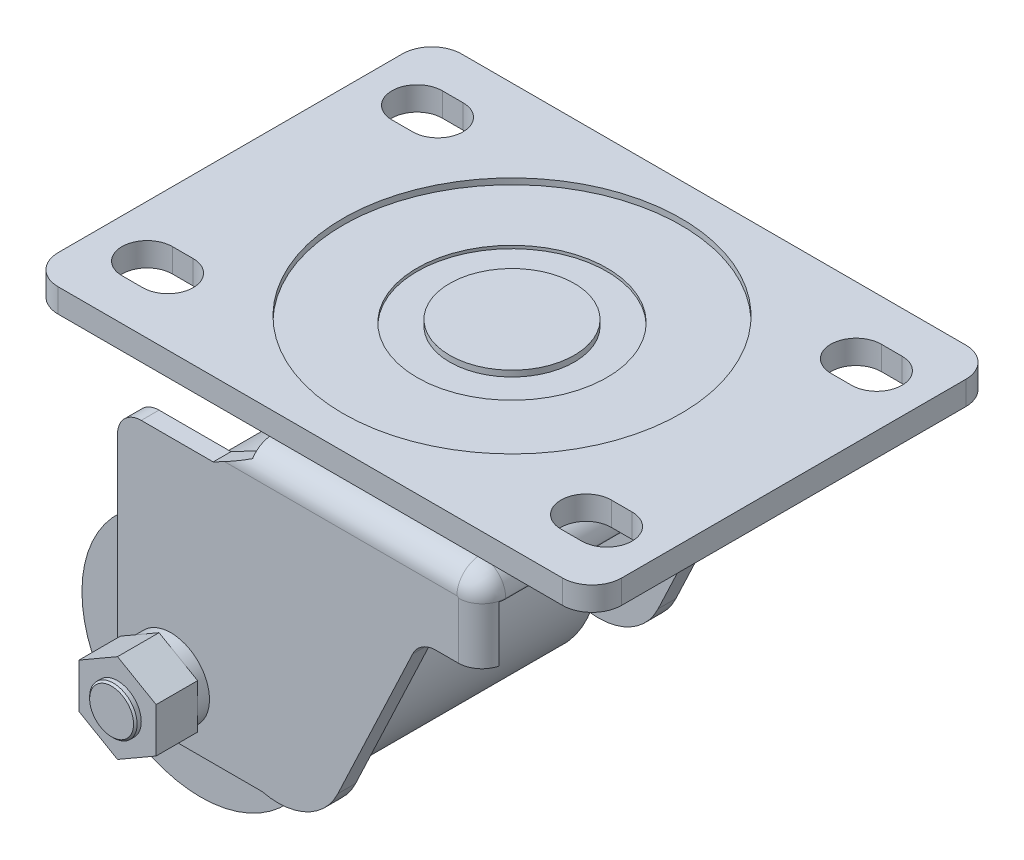
SolidWorks part; units mm, degrees
material "Plain Carbon Steel"
ref_plane "前视基准面" through (0, 0, 0) normal (0, 0, 1) x (1, 0, 0)
ref_plane "上视基准面" through (0, 0, 0) normal (0, 1, 0) x (1, 0, 0)
ref_plane "右视基准面" through (0, 0, 0) normal (1, 0, 0) x (0, 0, -1)
sketch "草图1" plane through (0, 0, 0) normal (0, 1, 0) x (1, 0, 0)
  line L1 (-47.5, -34) -> (47.5, -34)
  line L2 (-47.5, -34) -> (-47.5, 34)
  line L3 (-47.5, 34) -> (47.5, 34)
  line L4 (47.5, -34) -> (47.5, 34)
  line L5 (-47.5, -34) -> (47.5, 34) construction
  line L6 (-47.5, 34) -> (47.5, -34) construction
  point P0 (0, 0)
  dimension "D1" = 95
  dimension "D2" = 68
extrude "凸台-拉伸1" add sketch "草图1" against normal blind 4
sketch "草图2" plane through (0, 0, 0) normal (0, 1, 0) x (1, 0, 0)
  line L0 (-38.75, 22.75) -> (-35.25, 22.75) construction
  line L1 (-38.75, 27) -> (-35.25, 27)
  line L2 (-38.75, 18.5) -> (-35.25, 18.5)
  line L3 (0, 0) -> (0, 45.9781) construction
  line L4 (0, 0) -> (-36.329, 0) construction
  line L5 (38.75, 22.75) -> (35.25, 22.75) construction
  line L6 (38.75, 27) -> (35.25, 27)
  line L7 (38.75, 18.5) -> (35.25, 18.5)
  line L8 (-38.75, -22.75) -> (-35.25, -22.75) construction
  line L9 (-38.75, -27) -> (-35.25, -27)
  line L10 (-38.75, -18.5) -> (-35.25, -18.5)
  line L11 (38.75, -22.75) -> (35.25, -22.75) construction
  line L12 (38.75, -27) -> (35.25, -27)
  line L13 (38.75, -18.5) -> (35.25, -18.5)
  arc A0 (-38.75, 27) -> (-38.75, 18.5) centre (-38.75, 22.75) ccw
  arc A1 (-35.25, 18.5) -> (-35.25, 27) centre (-35.25, 22.75) ccw
  arc A2 (38.75, 27) -> (38.75, 18.5) centre (38.75, 22.75) cw
  arc A3 (35.25, 18.5) -> (35.25, 27) centre (35.25, 22.75) cw
  arc A4 (-38.75, -27) -> (-38.75, -18.5) centre (-38.75, -22.75) cw
  arc A5 (-35.25, -18.5) -> (-35.25, -27) centre (-35.25, -22.75) cw
  arc A6 (38.75, -27) -> (38.75, -18.5) centre (38.75, -22.75) ccw
  arc A7 (35.25, -18.5) -> (35.25, -27) centre (35.25, -22.75) ccw
  point P2 (-37, 22.75)
  point P13 (37, 22.75)
  point P20 (-37, -22.75)
  point P27 (37, -22.75)
  dimension "D2" = 70.5
  dimension "D4" = 45.5
  dimension "D1" = 3.5
  dimension "D3" = 8.5
extrude "切除-拉伸1" cut sketch "草图2" against normal blind 20
sketch "草图3" plane through (0, 0, 0) normal (0, 0, 1) x (1, 0, 0)
  line L0 (0, -4) -> (0, -13)
  line L1 (-47.5, -4) -> (47.5, -4) construction
  line L2 (0, -13) -> (26, -13)
  line L3 (26, -13) -> (26, -6)
  line L4 (26, -6) -> (21.6, -6)
  line L5 (21.6, -6) -> (21.6, -4)
  line L6 (21.6, -4) -> (0, -4)
  dimension "D1" = 2
  dimension "D2" = 7
  dimension "D3" = 21.6
  dimension "D4" = 26
revolve "旋转1" add sketch "草图3" angle 360 about L0
fillet "圆角3" radius 4 1 edges at (-26, -13, 0)
sketch "草图4" plane through (0, 0, 0) normal (0, 0, 1) x (1, 0, 0)
  line L0 (0, -13) -> (19.2133, -13)
  line L1 (-26, -13) -> (26, -13) construction
  line L2 (23.4482, -17.2349) -> (23.4482, -26.7145)
  line L3 (23.4482, -26.7145) -> (15.6902, -26.7145)
  line L4 (11.76, -29.205) -> (-0.8636, -55.9388)
  line L5 (-13.6125, -62) -> (-29, -62)
  line L6 (-38, -53) -> (-38, -18)
  line L7 (-38, -18) -> (-21.8692, -18)
  line L8 (-21.8692, -18) -> (-15.8691, -14.8424)
  line L9 (-15.8691, -14.8424) -> (-15.8691, -13)
  line L10 (-15.8691, -13) -> (0, -13)
  line L11 (-47.5, -4) -> (47.5, -4) construction
  line L12 (-47.5, -4) -> (-47.5, 0) construction
  arc A0 (19.2133, -13) -> (23.4482, -17.2349) centre (19.2133, -17.2349) cw
  arc A1 (15.6902, -26.7145) -> (11.76, -29.205) centre (15.6902, -31.0607) ccw
  arc A2 (-0.8636, -55.9388) -> (-13.6125, -62) centre (-10.9412, -51.1802) cw
  arc A3 (-29, -62) -> (-38, -53) centre (-29, -53) cw
  dimension "D1" = 9
  dimension "D4" = 53
  dimension "D2" = 14
  dimension "D3" = 9.5
extrude "凸台-拉伸2" add sketch "草图4" along normal mid plane 57
sketch "草图5" plane through (-38, 0, 0) normal (-1, 0, 0) x (0, 0, 1)
  line L0 (-28.5, -62.3249) -> (28.5, -62.3249) construction
  line L1 (-25.5, -62.3249) -> (25.5, -62.3249)
  line L2 (-25.5, -62.3249) -> (-25.5, -17.3249)
  line L3 (-25.5, -17.3249) -> (25.5, -17.3249)
  line L4 (25.5, -62.3249) -> (25.5, -17.3249)
  line L5 (-28.5, -18) -> (-28.5, -53) construction
  line L6 (28.5, -18) -> (28.5, -53) construction
  dimension "D1" = 45
  dimension "D2" = 3
  dimension "D3" = 3
extrude "切除-拉伸2" cut sketch "草图5" against normal through all both and the other way through all
fillet "圆角1" radius 5 4 edges at (47.5, -2, -34) (-47.5, -2, -34) (-47.5, -2, 34) (47.5, -2, 34)
sketch "草图6" plane through (0, 0, 0) normal (0, 0, 1) x (1, 0, 0)
  circle A0 centre (-29, -53) radius 20
  dimension "D1" = 40
extrude "凸台-拉伸3" add sketch "草图6" along normal mid plane 47 separate body
sketch "草图7" plane through (0, 0, 0) normal (0, 0, 1) x (1, 0, 0)
  circle A0 centre (-29, -53) radius 11.95
  dimension "D1" = 23.9
extrude "凸台-拉伸4" add sketch "草图7" along normal mid plane 50
sketch "草图8" plane through (0, 0, -28.5) normal (0, 0, -1) x (-1, 0, 0)
  line L1 (29, -45.4944) -> (22.5, -49.2472)
  line L2 (22.5, -49.2472) -> (22.5, -56.7528)
  line L3 (22.5, -56.7528) -> (29, -60.5056)
  line L4 (29, -60.5056) -> (35.5, -56.7528)
  line L5 (35.5, -56.7528) -> (35.5, -49.2472)
  line L6 (35.5, -49.2472) -> (29, -45.4944)
  circle A0 centre (29, -53) radius 6.5 construction
  dimension "D1" = 13
extrude "凸台-拉伸5" add sketch "草图8" along normal blind 6
sketch "草图9" plane through (0, 0, 28.5) normal (0, 0, 1) x (1, 0, 0)
  circle A0 centre (-29, -53) radius 6.5
  dimension "D1" = 13
extrude "凸台-拉伸6" add sketch "草图9" along normal blind 2
sketch "草图10" plane through (0, 0, 30.5) normal (0, 0, 1) x (1, 0, 0)
  line L1 (-29, -45.4944) -> (-35.5, -49.2472)
  line L2 (-35.5, -49.2472) -> (-35.5, -56.7528)
  line L3 (-35.5, -56.7528) -> (-29, -60.5056)
  line L4 (-29, -60.5056) -> (-22.5, -56.7528)
  line L5 (-22.5, -56.7528) -> (-22.5, -49.2472)
  line L6 (-22.5, -49.2472) -> (-29, -45.4944)
  circle A0 centre (-29, -53) radius 6.5 construction
  dimension "D1" = 13
extrude "凸台-拉伸7" add sketch "草图10" along normal blind 7
sketch "草图11" plane through (0, 0, 37.5) normal (0, 0, 1) x (1, 0, 0)
  circle A0 centre (-29, -53) radius 4
  dimension "D1" = 8
extrude "凸台-拉伸8" add sketch "草图11" along normal blind 1
chamfer "倒角1" distance 0.3 angle 45 1 edges at (-25, -53, 38.5)
fillet "圆角4" radius 4 3 edges at (-20.5863, -17.3249, 0) (-38, -18, -27) (-38, -18, 27)
sketch "草图12" plane through (0, 0, 0) normal (0, 1, 0) x (1, 0, 0)
  circle A0 centre (0, 0) radius 28.5
  dimension "D1" = 57
extrude "切除-拉伸3" cut sketch "草图12" against normal blind 1
sketch "草图13" plane through (0, -1, 0) normal (0, 1, 0) x (1, 0, 0)
  circle A0 centre (0, 0) radius 16
  dimension "D1" = 32
extrude "切除-拉伸4" cut sketch "草图13" against normal blind 0.5
sketch "草图14" plane through (0, -1.5, 0) normal (0, 1, 0) x (1, 0, 0)
  circle A0 centre (0, 0) radius 10.5
  dimension "D1" = 21
extrude "凸台-拉伸9" add sketch "草图14" along normal blind 1
fillet "圆角5" radius 4 6 edges at (23.4482, -21.9747, -28.5) (22.2078, -14.2404, -28.5) (23.4482, -21.9747, 28.5) (22.2078, -14.2404, 28.5) (1.6721, -13, -28.5) (1.6721, -13, 28.5)
